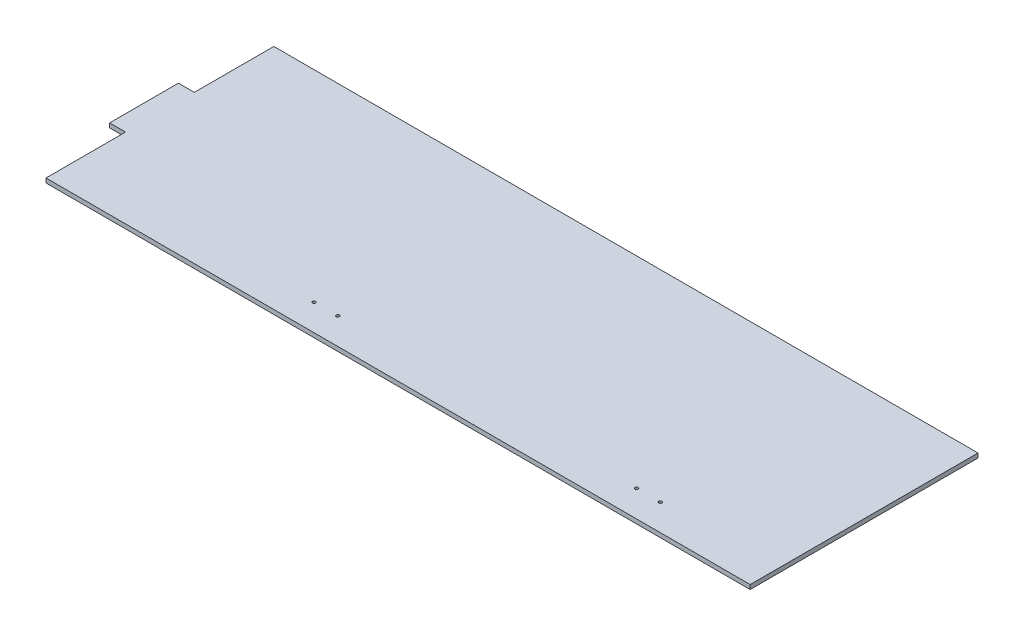
SolidWorks part; units mm, degrees
ref_plane "Front Plane" through (0, 0, 0) normal (0, 0, 1) x (1, 0, 0)
ref_plane "Top Plane" through (0, 0, 0) normal (0, 1, 0) x (1, 0, 0)
ref_plane "Right Plane" through (0, 0, 0) normal (1, 0, 0) x (0, 0, -1)
sketch "Sketch1" plane through (0, 0, 0) normal (0, 1, 0) x (1, 0, 0)
  line L0 (-280, 21.6257) -> (-270, 21.6257)
  line L1 (-270, 71.6257) -> (270, 71.6257)
  line L2 (-270, 71.6257) -> (-270, 21.6257)
  line L3 (-270, -71.6257) -> (270, -71.6257)
  line L4 (270, 71.6257) -> (270, -71.6257)
  line L5 (-270, 71.6257) -> (270, -71.6257) construction
  line L6 (-270, -71.6257) -> (270, 71.6257) construction
  line L7 (-280, 21.6257) -> (-280, -21.6257)
  line L8 (-280, -21.6257) -> (-270, -21.6257)
  line L9 (-270, -21.6257) -> (-270, -71.6257)
  line L10 (-270, 22.6702) -> (-270, 21.6257) construction
  line L11 (172.78, 71.6257) -> (172.78, -71.6257)
  line L13 (177.78, 62.3) -> (177.78, -62.3) construction
  circle A5 centre (99.6713, -54.974) radius 1 construction
  circle A6 centre (84.6713, -54.974) radius 1 construction
  circle A7 centre (-103.1287, -54.974) radius 1 construction
  circle A8 centre (-118.1287, -54.974) radius 1 construction
  circle A9 centre (99.6713, -54.974) radius 1
  circle A10 centre (84.6713, -54.974) radius 1
  circle A11 centre (-103.1287, -54.974) radius 1
  circle A12 centre (-118.1287, -54.974) radius 1
  point P4 (0, 0)
  dimension "D1" = 50
  dimension "D2" = 50
  dimension "D3" = 5
  dimension "D6" = 10
  dimension "D7" = 540
  dimension "D8" = 143.2513
extrude "Boss-Extrude1" add sketch "Sketch1" along normal blind 2.7432 from offset 2 contours L8 L9 L3 L4 L1 L2 L0 L7 region at (-50.1513, 0, -0.0108)
